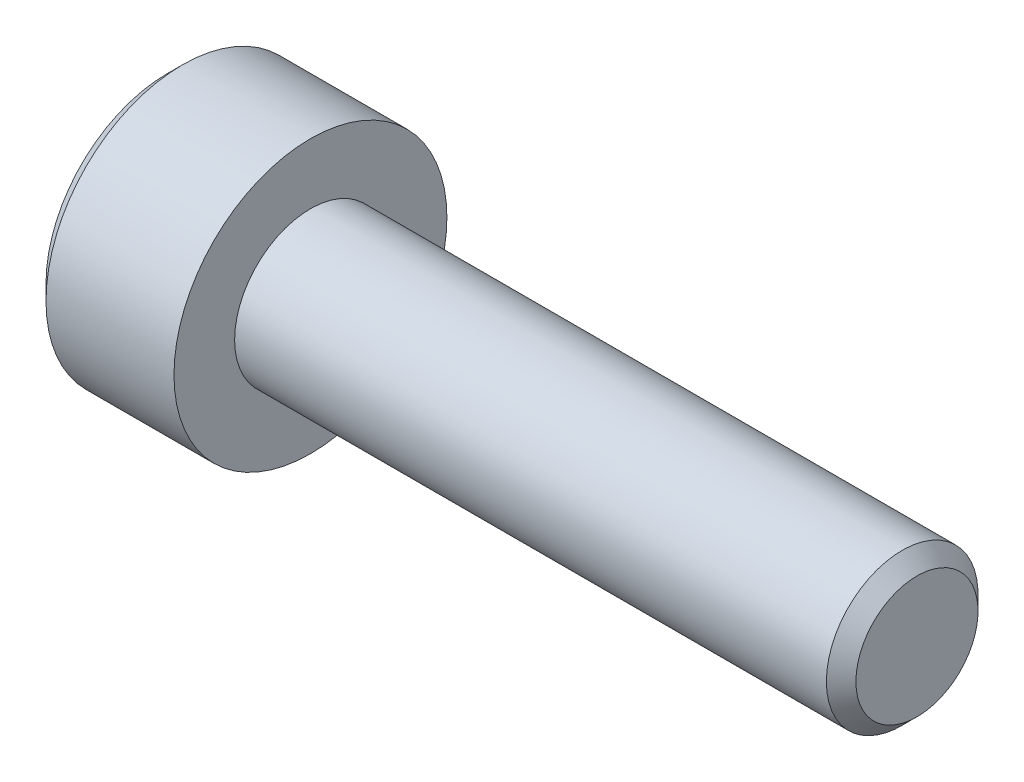
SolidWorks part; units mm, degrees
ref_plane "前视基准面" through (0, 0, 0) normal (0, 0, 1) x (1, 0, 0)
ref_plane "上视基准面" through (0, 0, 0) normal (0, 1, 0) x (1, 0, 0)
ref_plane "右视基准面" through (0, 0, 0) normal (1, 0, 0) x (0, 0, -1)
sketch "草图1" plane through (0, 0, 0) normal (0, 0, 1) x (1, 0, 0)
  line L0 (-2.36, 0) -> (-2.36, 2)
  line L1 (-2.36, 2) -> (-2.11, 2.25)
  line L2 (-2.11, 2.25) -> (0, 2.25)
  line L3 (0, 2.25) -> (0, 1.25)
  line L4 (0, 1.25) -> (9.7565, 1.25)
  line L5 (9.7565, 1.25) -> (10, 1.0065)
  line L6 (10, 1.0065) -> (10, 0)
  line L7 (10, 0) -> (-2.36, 0)
  line L8 (10, 0) -> (-2.36, 0) construction
revolve "旋转1" add sketch "草图1" angle 360 about L8 reverse direction yes
cosmetic thread "装饰螺纹线1" parameters "D1"=9.4782, "D2"=2.013
ref_plane "基准面4" through (-2.36, 0, 0) normal (1, 0, 0) x (0, 0, -1)
sketch "草图2" plane through (-2.36, 0, 0) normal (1, 0, 0) x (0, 0, -1)
  line L0 (-1, 0.5774) -> (-1, -0.5774)
  line L1 (-1, -0.5774) -> (0, -1.1547)
  line L2 (0, -1.1547) -> (1, -0.5774)
  line L3 (1, -0.5774) -> (1, 0.5774)
  line L4 (1, 0.5774) -> (0, 1.1547)
  line L5 (0, 1.1547) -> (-1, 0.5774)
extrude "切除-拉伸1" cut sketch "草图2" along normal blind 1.1
sketch "草图3" plane through (0, 0, 0) normal (0, 0, 1) x (1, 0, 0)
  line L0 (-1.26, 0) -> (-1.26, 1)
  line L1 (-1.26, 1) -> (-0.6826, 0)
  line L2 (-0.6826, 0) -> (-1.26, 0)
  line L3 (-0.6826, 0) -> (-1.26, 0) construction
revolve "切除-旋转1" cut sketch "草图3" angle 360 about L3 reverse direction yes
ref_plane "SCW XY" through (0, 0, 0) normal (1, 0, 0) x (0, 0, -1)
ref_plane "SCW XZ" through (0, 0, 0) normal (0, -1, 0) x (-1, 0, 0)
ref_plane "SCW YZ" through (0, 0, 0) normal (0, 0, -1) x (-1, 0, 0)
ref_axis "SCW X" through (0, 0, 80.9) along (0, 0, -1)
ref_axis "SCW Y" through (0, -50, 0) along (0, 1, 0)
ref_axis "SCW Z" through (80.9, 0, 0) along (-1, 0, 0)
sketch3d "SCW"
  point P0 (0, 0, 0)
